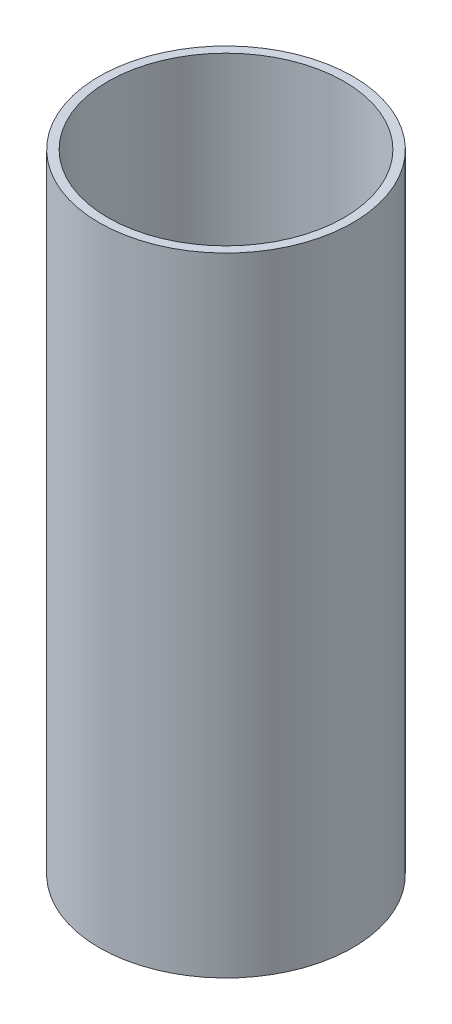
SolidWorks part; units mm, degrees
other "Top Tube"
ref_plane "Front Plane" through (0, 0, 0) normal (0, 0, 1) x (1, 0, 0)
ref_plane "Top Plane" through (0, 0, 0) normal (0, 1, 0) x (1, 0, 0)
ref_plane "Right Plane" through (0, 0, 0) normal (1, 0, 0) x (0, 0, -1)
sketch "Sketch1" plane through (0, 0, 0) normal (0, 0, 1) x (1, 0, 0)
  line L0 (55, 0) -> (-55, 0) construction
  line L1 (-20.5232, 228.6) -> (-19.1008, 228.6)
  line L2 (-20.5232, 228.6) -> (-20.5232, 330.2)
  line L3 (-20.5232, 330.2) -> (-19.1008, 330.2)
  line L4 (-19.1008, 228.6) -> (-19.1008, 330.2)
  line L5 (0, -55) -> (0, 55) construction
  line L6 (20.5232, 330.2) -> (19.1008, 330.2)
  line L7 (20.5232, 228.6) -> (20.5232, 330.2)
  line L8 (20.5232, 228.6) -> (19.1008, 228.6)
  line L9 (19.1008, 228.6) -> (19.1008, 330.2)
  line L10 (0, 0) -> (0, 330.2)
  dimension "D1" = 101.6
  dimension "9" = 228.6
  dimension "D2" = 41.0464
  dimension "D3" = 38.2016
revolve "Revolve1" add sketch "Sketch1" angle 360 about L10 region at (-19.812, 279.4, 0)
